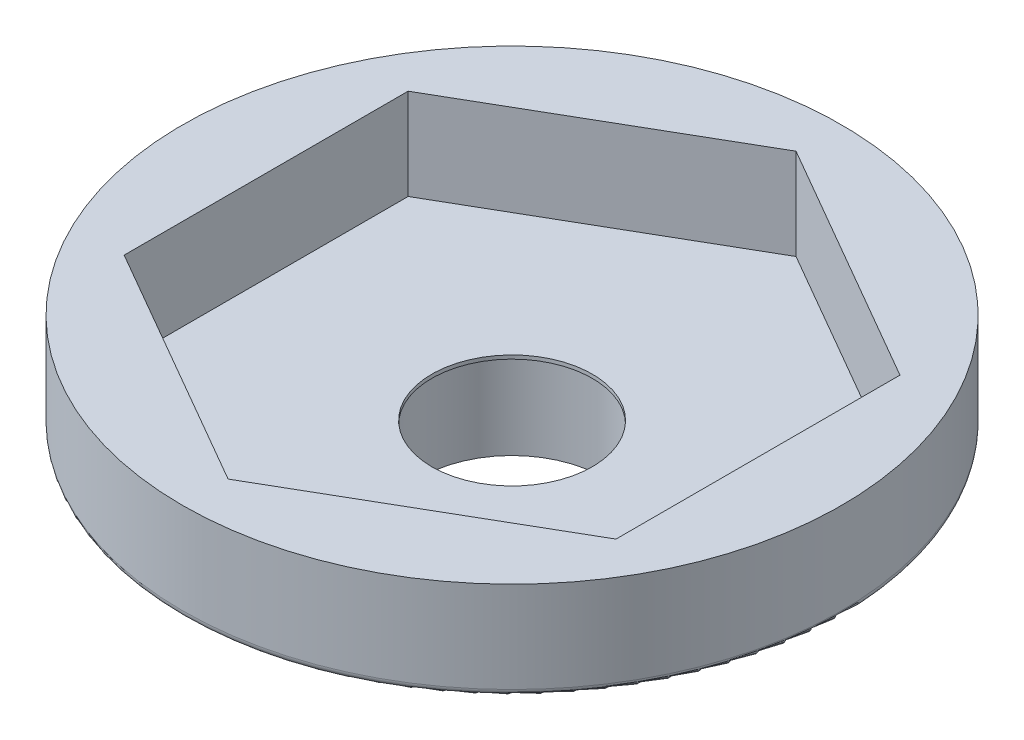
SolidWorks part; units mm, degrees
ref_plane "Front Plane" through (0, 0, 0) normal (0, 0, 1) x (1, 0, 0)
ref_plane "Top Plane" through (0, 0, 0) normal (0, 1, 0) x (1, 0, 0)
ref_plane "Right Plane" through (0, 0, 0) normal (1, 0, 0) x (0, 0, -1)
sketch "Sketch1" plane through (0, 0, 0) normal (0, 1, 0) x (1, 0, 0)
  line L0 (8.5598, -4.942) -> (9.9346, -5.7358) construction
  line L1 (8.5598, 4.942) -> (0, 9.884)
  line L2 (0, 9.884) -> (-8.5598, 4.942)
  line L3 (-8.5598, 4.942) -> (-8.5598, -4.942)
  line L4 (-8.5598, -4.942) -> (0, -9.884)
  line L5 (0, -9.884) -> (8.5598, -4.942)
  line L6 (8.5598, -4.942) -> (8.5598, 4.942)
  circle A0 centre (0, 0) radius 8.5598 construction
  circle A1 centre (0, 0) radius 11.4715
  dimension "D1" = 17.1196
  dimension "D2" = 1.5875
extrude "Boss-Extrude1" add sketch "Sketch1" along normal blind 3.175
sketch "Sketch2" plane through (0, 0, 0) normal (0, 1, 0) x (1, 0, 0)
  circle A0 centre (0, 0) radius 11.4715
  circle A1 centre (0, 0) radius 3.175
  circle A2 centre (0, 0) radius 11.4715 construction
  dimension "D1" = 6.35
extrude "Boss-Extrude2" add sketch "Sketch2" against normal blind 3.302
sketch "Sketch3" plane through (0, -3.302, 0) normal (0, -1, 0) x (-1, 0, 0)
  circle A0 centre (0, 0) radius 11.4715
  circle A1 centre (0, 0) radius 11.4715 construction
  circle A2 centre (0, 0) radius 2.794
  dimension "D1" = 5.588
extrude "Boss-Extrude3" add sketch "Sketch3" along normal offset from surface (0.127 mm away) 3.175 from surface up to face at (0, -3.302, 3.175) starting at plane "Top Plane"
sketch "Sketch4" plane through (0, 0, 0) normal (1, 0, 0) x (0, 0, -1)
  line L0 (11.4715, -3.302) -> (11.4715, 0)
  line L1 (11.4715, -3.302) -> (11.4715, 3.175) construction
  line L2 (11.4715, -3.302) -> (5.5563, -3.302)
  line L3 (-11.4715, -3.302) -> (11.4715, -3.302) construction
  line L4 (5.5563, -3.302) -> (5.5563, -0.762)
  line L5 (5.5563, -0.762) -> (11.2402, -0.253)
  line L6 (11.4715, -3.302) -> (11.4715, 3.175) construction
  line L7 (4.942, 0) -> (9.884, 0) construction
  line L8 (3.175, -3.302) -> (3.175, -0.127) construction
  line L9 (0, 0) -> (0, -3.302) construction
  arc A0 (11.4715, 0) -> (11.2402, -0.253) centre (11.2175, 0) cw
  dimension "D3" = 0.254
  dimension "D1" = 2.54
  dimension "D2" = 2.3813
revolve "Cut-Revolve1" cut sketch "Sketch4" angle 360 about L9
fillet "Fillet1" radius 2.54 1 edges at (0, -0.762, 5.5563)
